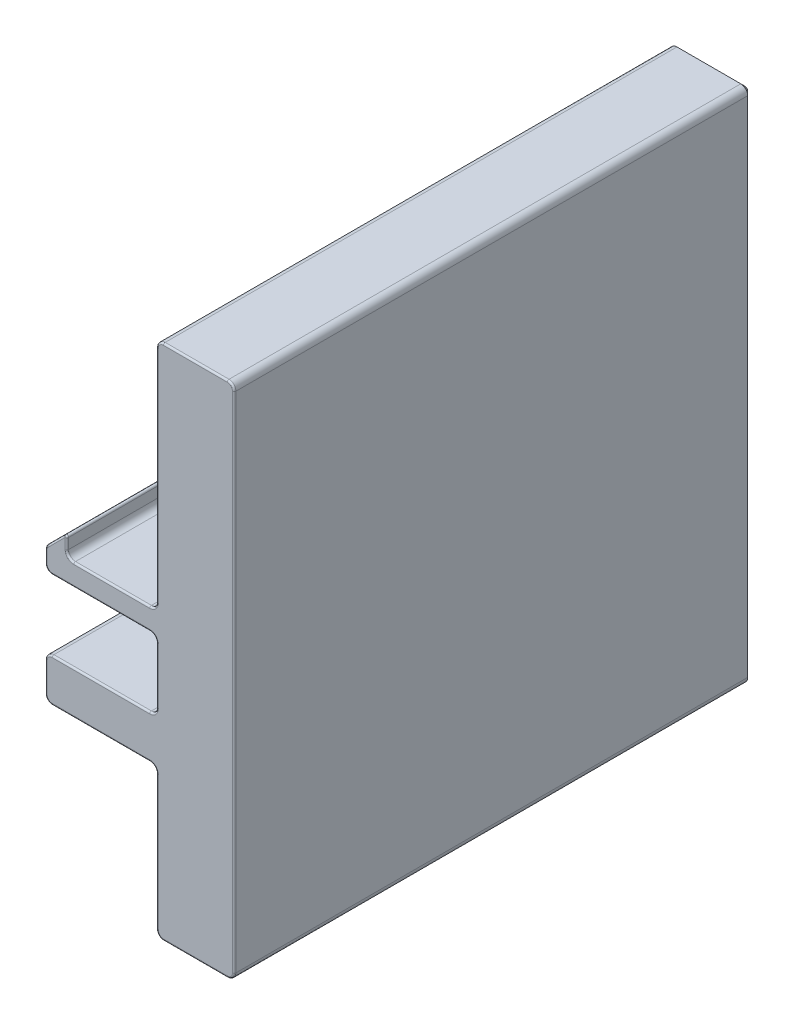
SolidWorks part; units mm, degrees
ref_plane "Front Plane" through (0, 0, 0) normal (0, 0, 1) x (1, 0, 0)
ref_plane "Top Plane" through (0, 0, 0) normal (0, 1, 0) x (1, 0, 0)
ref_plane "Right Plane" through (0, 0, 0) normal (1, 0, 0) x (0, 0, -1)
sketch "Sketch1" plane through (0, 0, 0) normal (0, 0, 1) x (1, 0, 0)
  line L0 (-0.127, 38.1) -> (-0.127, 20.955) construction
  line L1 (0, 0) -> (5.715, 0)
  line L2 (0, 0) -> (0, 10.922)
  line L3 (0, 38.1) -> (5.715, 38.1)
  line L4 (5.715, 0) -> (5.715, 38.1)
  line L9 (-0.127, 20.955) -> (-6.477, 20.955) construction
  line L10 (-6.477, 20.955) -> (-6.477, 38.1) construction
  line L11 (-6.477, 38.1) -> (-12.827, 38.1) construction
  line L12 (-12.827, 38.1) -> (-12.827, -6.35) construction
  line L13 (-12.827, -6.35) -> (-6.477, -6.35) construction
  line L14 (-6.477, -6.35) -> (-6.477, 10.795) construction
  line L15 (-6.477, 10.795) -> (-0.127, 10.795) construction
  line L16 (-0.127, 10.795) -> (-0.127, -6.35) construction
  line L17 (0, 20.828) -> (-6.604, 20.828)
  line L18 (-6.604, 20.828) -> (-6.604, 22.4155)
  line L19 (-6.604, 22.4155) -> (-8.1915, 20.828)
  line L20 (-8.1915, 20.828) -> (-8.1915, 19.2405)
  line L21 (-8.1915, 19.2405) -> (0, 19.2405)
  line L22 (0, 20.828) -> (0, 38.1)
  line L23 (0, 10.922) -> (-8.1915, 10.922)
  line L25 (0, 14.097) -> (-8.1915, 14.097)
  line L26 (-8.1915, 10.922) -> (-8.1915, 14.097)
  line L27 (0, 14.097) -> (0, 19.2405)
  dimension "D1" = 5.715
  dimension "D2" = 38.1
  dimension "D3" = 0.254
  dimension "D4" = 12.7
  dimension "D5" = 44.45
  dimension "0.25" = 6.35
  dimension "D6" = 10.16
  dimension "D7" = 0.127
  dimension "D8" = 0.254
  dimension "D9" = 1.5875
  dimension "D10" = 1.5875
  dimension "D11" = 45
  dimension "D12" = 0.254
  dimension "D13" = 3.175
extrude "Boss-Extrude1" add sketch "Sketch1" along normal blind 38.1 contours L4 L3 L22 L17 L18 L19 L20 L21 L27 L25 L26 L23 L2 L1
fillet "Fillet1" radius 0.508 13 edges at (0, 38.1, 19.05) (0, 20.828, 19.05) (0, 0, 19.05) (-8.1915, 10.922, 19.05) (-8.1915, 14.097, 19.05) (-8.1915, 20.828, 19.05) (5.715, 38.1, 19.05) (5.715, 0, 19.05) (0, 10.922, 19.05) (-6.604, 20.828, 19.05) (0, 14.097, 19.05) (0, 19.2405, 19.05) (-8.1915, 19.2405, 19.05)
fillet "Fillet2" radius 0.127 1 edges at (-6.604, 22.4155, 19.05)
chamfer "Chamfer1" distance 0.3 angle 45 9 edges at (-4.0957, 14.097, 0) (-8.1915, 12.5095, 0) (-4.0957, 10.922, 0) (-0.1488, 10.7732, 0) (0, 5.461, 0) (0.1488, 0.1488, 0) (2.8575, 0, 0) (5.5662, 0.1488, 0) (5.715, 19.05, 0) tangent propagation no
sketch "Sketch4" plane through (0, 0, 0) normal (0, 0, -1) x (-1, 0, 0)
  line L0 (6.904, 21.6912) -> (7.8306, 20.7647)
  line L1 (7.8915, 13.589) -> (-0.3, 13.589)
  line L2 (7.8915, 13.589) -> (7.8915, 20.6176)
  line L3 (6.904, 21.6912) -> (-0.3, 21.6912)
  line L4 (-0.3, 13.589) -> (-0.3, 21.6912)
  line L5 (-0.3, 21.336) -> (-0.3, 37.592) construction
  arc A1 (7.8915, 20.6176) -> (7.8306, 20.7647) centre (7.6835, 20.6176) ccw construction
  arc A2 (7.8915, 20.6176) -> (7.8306, 20.7647) centre (7.6835, 20.6176) ccw
extrude "Boss-Extrude3" [suppressed] add sketch "Sketch4" against normal blind 0.2
sketch "Sketch3" plane through (0, 19.2405, 0) normal (0, -1, 0) x (1, 0, 0)
  line L0 (-8.1915, 19.1144) -> (0, 25.4)
  line L1 (-8.1915, 38.1) -> (-8.1915, 0) construction
  line L2 (0, 38.1) -> (0, 0) construction
  line L3 (0, 25.4) -> (-8.1915, 31.6856)
  line L4 (-8.1915, 31.6856) -> (-8.1915, 19.1144)
  line L5 (0, 0) -> (5.715, 0) construction
  dimension "D1" = 75
  dimension "D2" = 25.4
extrude "Cut-Extrude2" [suppressed] cut sketch "Sketch3" against normal through all
pattern_linear "LPattern2" [suppressed] count 2 spacing 25.4 of bodies 104
fillet "Fillet3" radius 0.127 28 edges at (-6.4552, 20.9768, 38.1) (-3.302, 20.828, 38.1) (-0.1488, 20.9768, 38.1) (0, 29.464, 38.1) (0.1488, 37.9512, 38.1) (2.8575, 38.1, 38.1) (5.5662, 37.9512, 38.1) (5.715, 19.05, 38.1) (5.5662, 0.1488, 38.1) (2.8575, 0, 38.1) (0.1488, 0.1488, 38.1) (0, 5.461, 38.1) (-0.1488, 10.7732, 38.1) (-4.0957, 10.922, 38.1) (-8.0427, 11.0708, 38.1) (-8.1915, 12.5095, 38.1) (-8.0427, 13.9482, 38.1) (-4.0957, 14.097, 38.1) (-0.1488, 14.2458, 38.1) (0, 16.6687, 38.1) (-0.1488, 19.0917, 38.1) (-4.0957, 19.2405, 38.1) (-8.0427, 19.3893, 38.1) (-8.1915, 20.183, 38.1) (-8.1528, 20.812, 38.1) (-7.4318, 21.5877, 38.1) (-6.6824, 22.2262, 38.1) (-6.604, 21.7224, 38.1)
